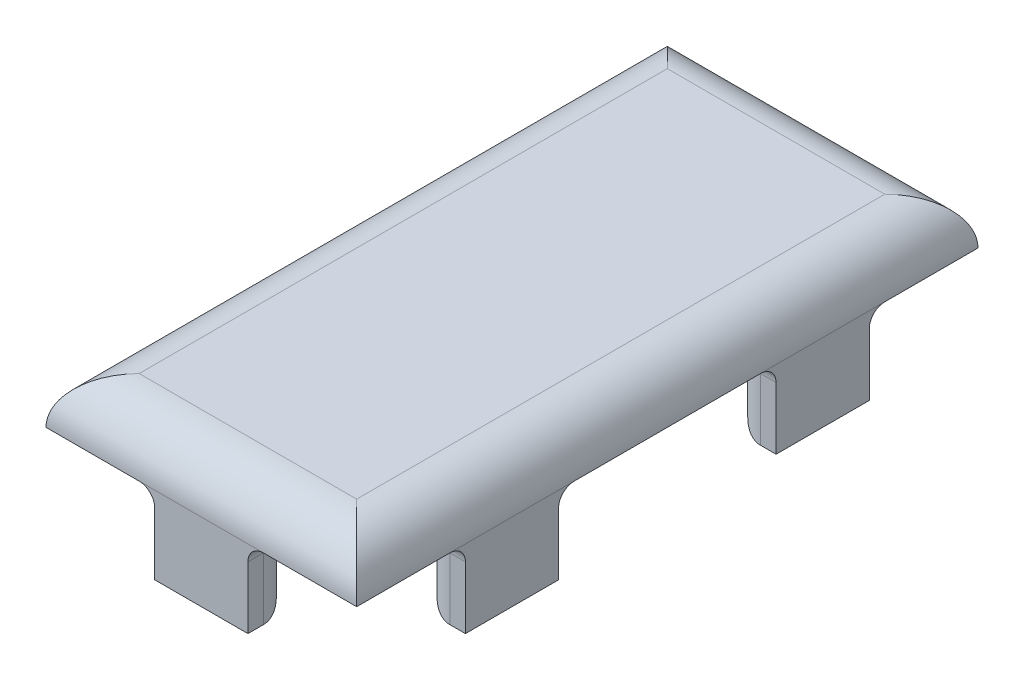
SolidWorks part; units mm, degrees
ref_plane "Plano frontal" through (0, 0, 0) normal (0, 0, 1) x (1, 0, 0)
ref_plane "Plano superior" through (0, 0, 0) normal (0, 1, 0) x (1, 0, 0)
ref_plane "Plano direito" through (0, 0, 0) normal (1, 0, 0) x (0, 0, -1)
sketch "Esboço1" plane through (0, 0, 0) normal (0, 1, 0) x (1, 0, 0)
  line L0 (0, 40) -> (20, 40)
  line L1 (20, 40) -> (20, 0)
  line L2 (20, 0) -> (0, 0)
  line L3 (0, 0) -> (0, 40)
  point P4 (0, 0)
  dimension "D1" = 20
  dimension "D2" = 40
extrude "Ressalto-extrusão1" add sketch "Esboço1" along normal blind 3
fillet "Filete1" radius 3 4 edges at (10, 3, -40) (20, 3, -20) (10, 3, 0) (0, 3, -20)
sketch "Esboço2" plane through (0, 0, 0) normal (0, -1, 0) x (1, 0, 0)
  line L0 (10, 0) -> (10, -40) construction
  line L1 (0, 0) -> (20, 0) construction
  line L2 (20, -40) -> (0, -40) construction
  line L3 (0, -20) -> (20, -20) construction
  line L4 (7, -3) -> (13, -3)
  line L5 (7, -3) -> (7, 0)
  line L6 (7, 0) -> (13, 0)
  line L7 (13, -3) -> (13, 0)
  line L8 (7, -3) -> (13, 0) construction
  line L9 (7, 0) -> (13, -3) construction
  line L10 (0, -40) -> (0, 0) construction
  line L11 (20, 0) -> (20, -40) construction
  line L12 (7, -40) -> (13, -37) construction
  line L13 (7, -37) -> (13, -40) construction
  line L14 (13, -37) -> (13, -40)
  line L15 (7, -40) -> (13, -40)
  line L16 (7, -37) -> (7, -40)
  line L17 (7, -37) -> (13, -37)
  line L18 (3, -33) -> (0, -33)
  line L19 (17, -7) -> (20, -7)
  line L20 (17, -7) -> (17, -13)
  line L21 (17, -13) -> (20, -13)
  line L22 (20, -7) -> (20, -13)
  line L23 (17, -7) -> (20, -13) construction
  line L24 (17, -13) -> (20, -7) construction
  line L25 (17, -27) -> (20, -27)
  line L26 (17, -27) -> (17, -33)
  line L27 (17, -33) -> (20, -33)
  line L28 (20, -27) -> (20, -33)
  line L29 (17, -27) -> (20, -33) construction
  line L30 (17, -33) -> (20, -27) construction
  line L31 (0, -27) -> (0, -33)
  line L32 (3, -27) -> (0, -27)
  line L33 (3, -27) -> (3, -33)
  line L34 (3, -13) -> (0, -13)
  line L35 (0, -7) -> (0, -13)
  line L36 (3, -7) -> (0, -7)
  line L37 (3, -7) -> (3, -13)
  point P6 (10, -1.5)
  point P21 (10, -38.5)
  point P22 (18.5, -10)
  point P27 (18.5, -30)
  dimension "D1" = 3
  dimension "D2" = 6
  dimension "D3" = 7
  dimension "D4" = 7
extrude "Ressalto-extrusão2" add sketch "Esboço2" along normal blind 5
fillet "Filete2" radius 2 18 edges at (7, -2.5, -37) (13, -2.5, -37) (10, -5, -37) (3, -2.5, -33) (3, -2.5, -27) (3, -5, -30) (17, -2.5, -33) (17, -5, -30) (17, -2.5, -27) (17, -2.5, -13) (17, -5, -10) (17, -2.5, -7) (7, -2.5, -3) (13, -2.5, -3) (10, -5, -3) (3, -2.5, -13) (3, -2.5, -7) (3, -5, -10)
fillet "Filete3" radius 1 30 edges at (13, 0, -39.5) (12.4142, 0, -37.5858) (7, 0, -39.5) (7.5858, 0, -37.5858) (19.5, 0, -27) (17.5858, 0, -27.5858) (19.5, 0, -33) (17.5858, 0, -32.4142) (0.5, 0, -33) (2.4142, 0, -32.4142) (0.5, 0, -27) (2.4142, 0, -27.5858) (0.5, 0, -13) (2.4142, 0, -12.4142) (0.5, 0, -7) (2.4142, 0, -7.5858) (19.5, 0, -7) (17.5858, 0, -7.5858) (19.5, 0, -13) (17.5858, 0, -12.4142) (7, 0, -0.5) (7.5858, 0, -2.4142) (13, 0, -0.5) (12.4142, 0, -2.4142) (10, 0, -37) (17, 0, -30) (3, 0, -30) (3, 0, -10) (17, 0, -10) (10, 0, -3)
